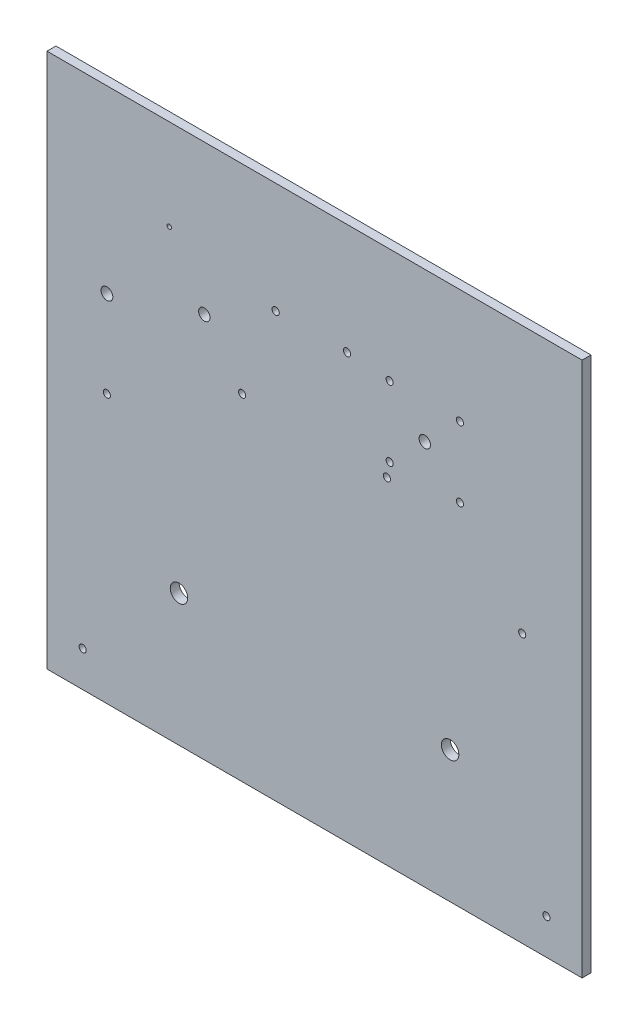
SolidWorks part; units mm, degrees
ref_plane "Front Plane" through (0, 0, 0) normal (0, 0, 1) x (1, 0, 0)
ref_plane "Top Plane" through (0, 0, 0) normal (0, 1, 0) x (1, 0, 0)
ref_plane "Right Plane" through (0, 0, 0) normal (1, 0, 0) x (0, 0, -1)
sketch "Sketch1" plane through (0, 0, 0) normal (0, 0, 1) x (1, 0, 0)
  line L0 (0, 7.9331) -> (50.8, 7.9331) construction
  line L2 (-120.1645, -103.1124) -> (-120.1645, -41.3962) construction
  line L6 (218.186, 86.7928) -> (-162.814, 86.7928)
  line L13 (218.186, 86.7928) -> (218.186, -294.2072)
  line L14 (-162.814, 86.7928) -> (-162.814, -294.2072)
  line L16 (-162.814, -294.2072) -> (218.186, -294.2072)
  circle A0 centre (106.172, -19.5453) radius 4.064
  circle A1 centre (79.2312, -55.0227) radius 2.54
  circle A2 centre (192.786, -268.8072) radius 2.54
  circle A3 centre (-137.414, -268.8072) radius 2.54
  circle A4 centre (131.172, 5.4547) radius 2.54
  circle A5 centre (175.5365, -103.1124) radius 2.54
  circle A6 centre (131.172, -44.5453) radius 2.54
  circle A7 centre (124.206, -200.4101) radius 6.223
  circle A8 centre (-68.834, -200.4101) radius 6.223
  circle A9 centre (81.172, -44.5453) radius 2.54
  circle A10 centre (-120.1645, -103.1124) radius 2.54
  circle A11 centre (81.172, 5.4547) radius 2.54
  circle A12 centre (0, 7.9331) radius 2.5797
  circle A13 centre (50.8, 7.9331) radius 2.5797
  circle A14 centre (-23.8592, -55.0227) radius 2.54
  circle A15 centre (-50.8, -19.5453) radius 4.064
  circle A17 centre (-75.7145, 22.1038) radius 1.5875
  dimension "D1" = 4
  dimension "D2" = 50.8
  dimension "D3" = 5.1594
extrude "Boss-Extrude1" add sketch "Sketch1" along normal blind 6.35
hole_wizard "3/8-24 Tapped Hole2" positions "Sketch5" profile "Sketch4" tap size "3/8-24" standard "Ansi Inch" end condition through all
sketch "Sketch5" plane through (0, 0, 6.35) normal (0, 0, 1) x (1, 0, 0)
  line L0 (-120.1645, -103.1124) -> (-120.1645, -41.3904) construction
  point P0 (-120.1645, -41.3904)
sketch "Sketch4" plane through (-120.1645, -41.3904, 6.35) normal (1, 0, 0) x (0, -1, 0)
  line L0 (0, 0) -> (0, 6.35)
  line L1 (0, 6.35) -> (4.2164, 6.35)
  line L2 (4.2164, 6.35) -> (4.2164, 0)
  line L5 (4.2164, 0) -> (0, 0)
  line L11 (0, -6.35) -> (0, 107.95) construction
  dimension "Thru Tap Drill Dia." = 8.4328
  dimension "Thru Tap Drill Depth" = 6.35
cosmetic thread "Hole Thread2" parameters "D2"=9.525
